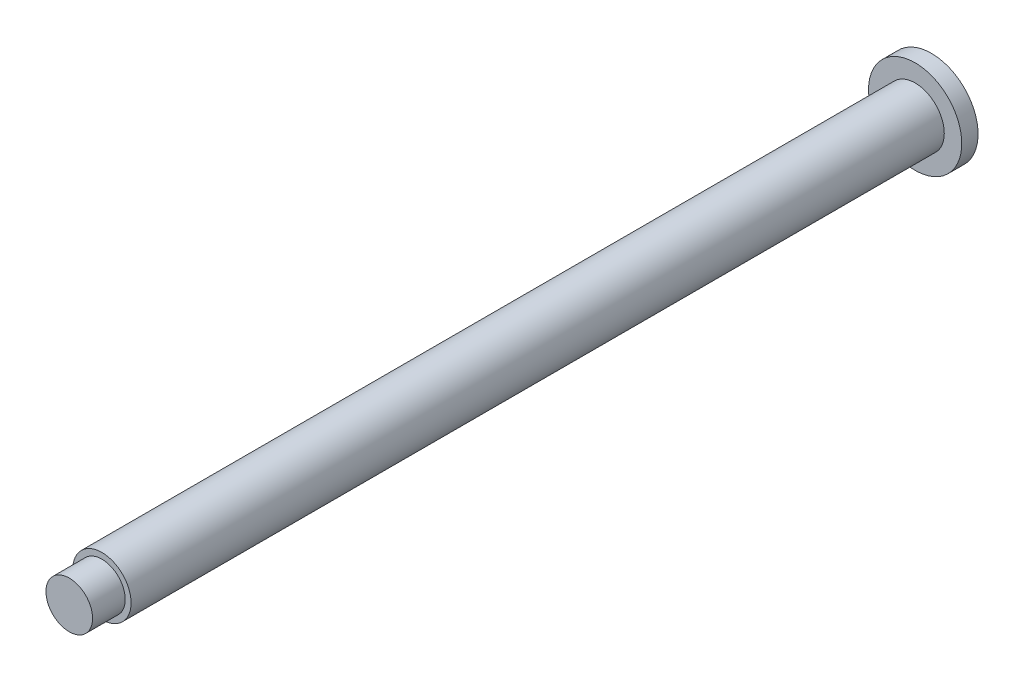
SolidWorks part; units mm, degrees
ref_plane "Front Plane" through (0, 0, 0) normal (1, 0, 0) x (0, 1, 0)
ref_plane "Top Plane" through (0, 0, 0) normal (0, 0, 1) x (0, 1, 0)
ref_plane "Right Plane" through (0, 0, 0) normal (0, 1, 0) x (-1, 0, 0)
sketch "Sketch1" plane through (0, 0, 0) normal (0, 0, 1) x (0, 1, 0)
  circle A0 centre (0, 0) radius 2.5
extrude "Boss-Extrude1" add sketch "Sketch1" along normal blind 69.75 contours A0
sketch "Sketch2" plane through (0, 0, 0) normal (0, 0, -1) x (1, 0, 0)
  circle A0 centre (0, 0) radius 4
extrude "Boss-Extrude2" add sketch "Sketch2" along normal blind 1.4
sketch "Sketch3" plane through (0, 0, -1.4) normal (0, 0, -1) x (1, 0, 0)
  circle A0 centre (0, 0) radius 2.05
extrude "Cut-Extrude1" cut sketch "Sketch3" against normal blind 3
sketch "Sketch4" plane through (0, 0, 69.75) normal (0, 0, 1) x (1, 0, 0)
  circle A0 centre (0, 0) radius 2
extrude "Boss-Extrude3" add sketch "Sketch4" along normal blind 2.8
equation "\"whitekey_cutout_length\"= 101.5"
equation "\"key_mount_recess_length\"=50"
equation "\"key_mount_recess_height\"=12.5"
equation "\"key_mount_recess_depth\"=1.5"
equation "\"wall_thickness\"=10"
equation "\"guide_brace_height\"=20"
equation "\"guide_brace_thickness\"=2"
equation "\"dowel_recess_depth\"=9"
equation "\"dowel_recess_offset\"=3"
equation "\"base_mount_height\"=40"
equation "\"base_rear_length\"=80"
equation "\"base_front_length\"=111.5"
equation "\"screw_hole_wall_offset\"=7.25"
equation "\"screw_hole_edge_inset\"=4.5"
equation "\"screw_hole_diameter\"=3.8"
equation "\"screw_head_hole_diameter\"=6.7"
equation "\"screw_nut_hole_side_len\"=3.5"
equation "\"screw_nut_recess_offset\"=0.3"
equation "\"screw_head_and_nut_recess_depth\"=2.5"
equation "\"screw_shaft_diameter\"=3.5"
equation "\"switch_board_width\"=30"
equation "\"switch_board_wall_offset\"=11.5"
equation "\"heatset_insert_hole_diameter\"=4.8"
equation "\"heatset_insert_hole_depth\"=3.8"
equation "\"front_rear_panel_width\"=23.75"
equation "\"rod_length_adj\"=0.5"
equation "\"rod_insert_length\"=2.8"
equation "\"D1@Boss-Extrude3\"=\"rod_insert_length\""
equation "\"D1@Boss-Extrude2\"=2-\"rod_length_adj\"-0.1"
equation "\"D1@Boss-Extrude1\"=\"rod_length_adj\"+69.25mm"
